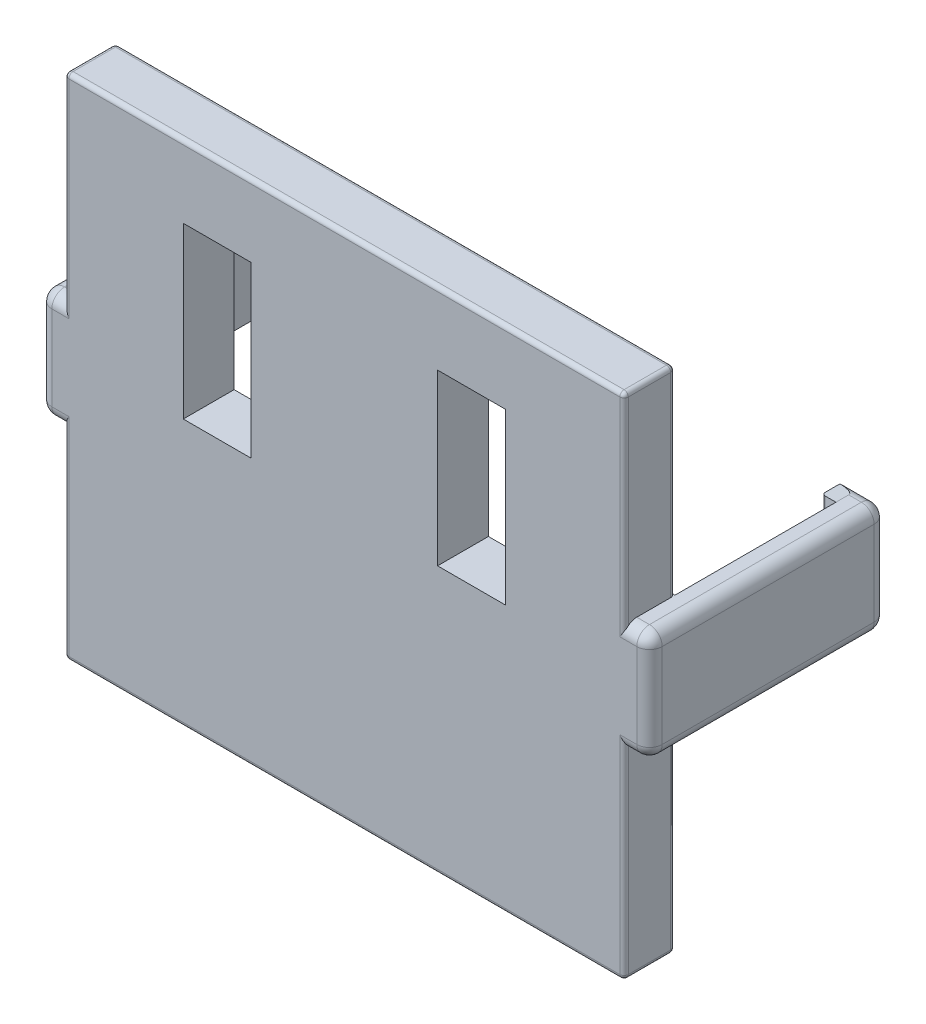
SolidWorks part; units mm, degrees
ref_plane "Plan de face" through (0, 0, 0) normal (0, 0, 1) x (1, 0, 0)
ref_plane "Plan de dessus" through (0, 0, 0) normal (0, 1, 0) x (1, 0, 0)
ref_plane "Plan de droite" through (0, 0, 0) normal (1, 0, 0) x (0, 0, -1)
sketch "Esquisse1" plane through (0, 0, 0) normal (0, 0, 1) x (1, 0, 0)
  line L1 (-16.5, 15) -> (16.5, 15)
  line L2 (-16.5, 15) -> (-16.5, -15)
  line L3 (-16.5, -15) -> (16.5, -15)
  line L4 (16.5, 15) -> (16.5, -15)
  line L5 (-16.5, 15) -> (16.5, -15) construction
  line L6 (-16.5, -15) -> (16.5, 15) construction
  point P0 (0, 0)
  dimension "D1" = 33
  dimension "D2" = 30
extrude "Boss.-Extru.1" add sketch "Esquisse1" along normal blind 3
sketch "Esquisse2" plane through (16.5, 0, 0) normal (1, 0, 0) x (0, 0, -1)
  line L0 (-3, -15) -> (-3, 15) construction
  line L1 (-3, 3.25) -> (11, 3.25)
  line L2 (-3, 3.25) -> (-3, -3.25)
  line L3 (-3, -3.25) -> (11, -3.25)
  line L4 (11, 3.25) -> (11, -3.25)
  line L5 (-3, -15) -> (0, -15) construction
  dimension "D1" = 11.75
  dimension "D2" = 6.5
  dimension "D3" = 14
extrude "Boss.-Extru.2" add sketch "Esquisse2" along normal blind 1.5
sketch "Esquisse3" plane through (16.5, 0, 0) normal (-1, 0, 0) x (0, 0, 1)
  line L0 (0, -3.25) -> (-11, -3.25) construction
  line L1 (-11, 3.25) -> (-9.5, 3.25)
  line L2 (-11, 3.25) -> (-11, -3.25)
  line L3 (-11, -3.25) -> (-9.5, -3.25)
  line L4 (-9.5, 3.25) -> (-9.5, -3.25)
  dimension "D1" = 1.5
extrude "Boss.-Extru.3" add sketch "Esquisse3" along normal blind 1 draft 10
fillet "Congé1" radius 0.75 1 edges at (18, -3.25, -4)
fillet "Congé2" radius 0.75 1 edges at (18, 3.25, -4)
fillet "Congé3" radius 0.75 5 edges at (17.7803, 3.0303, 3) (17.7803, -3.0303, 3) (18, 0, 3)
fillet "Congé4" radius 0.75 5 edges at (16.875, -3.25, -11) (17.7803, -3.0303, -11) (16.875, 3.25, -11) (17.7803, 3.0303, -11) (18, 0, -11)
fillet "Congé5" radius 0.25 1 edges at (15.5, 0, -10.8237)
fillet "Congé6" radius 0.25 1 edges at (15.5, 0, -9.6763)
sketch "Esquisse4" plane through (-16.5, 0, 0) normal (-1, 0, 0) x (0, 0, 1)
  line L0 (3, 15) -> (3, -15) construction
  line L1 (3, 3.25) -> (-11, 3.25)
  line L2 (3, 3.25) -> (3, -3.25)
  line L3 (3, -3.25) -> (-11, -3.25)
  line L4 (-11, 3.25) -> (-11, -3.25)
  line L5 (3, 15) -> (0, 15) construction
  line L6 (3, -15) -> (0, -15) construction
  dimension "D1" = 14
  dimension "D2" = 6.5
  dimension "D3" = 11.75
  dimension "D4" = 11.75
extrude "Boss.-Extru.4" add sketch "Esquisse4" along normal blind 1.5
sketch "Esquisse5" plane through (-16.5, 0, 0) normal (1, 0, 0) x (0, 0, -1)
  line L0 (11, -3.25) -> (0, -3.25) construction
  line L1 (11, 3.25) -> (9.5, 3.25)
  line L2 (11, 3.25) -> (11, -3.25)
  line L3 (11, -3.25) -> (9.5, -3.25)
  line L4 (9.5, 3.25) -> (9.5, -3.25)
  dimension "D1" = 1.5
extrude "Boss.-Extru.6" add sketch "Esquisse5" along normal blind 1 draft 10
fillet "Congé16" radius 0.75 1 edges at (-18, 0, 3)
fillet "Congé17" radius 0.75 3 edges at (-17.7803, -3.25, 2.7803) (-18, -3.25, -4.375)
fillet "Congé18" radius 0.75 3 edges at (-17.7803, 3.25, 2.7803) (-18, 3.25, -4.375)
fillet "Congé19" radius 0.75 5 edges at (-16.875, 3.25, -11) (-17.7803, 3.0303, -11) (-16.875, -3.25, -11) (-17.7803, -3.0303, -11) (-18, 0, -11)
fillet "Congé20" radius 0.25 1 edges at (-15.5, 0, -10.8237)
fillet "Congé21" radius 0.25 1 edges at (-15.5, 0, -9.6763)
fillet "Congé22" radius 0.25 1 edges at (0, 15, 0)
fillet "Congé23" radius 0.25 1 edges at (0, 15, 3)
fillet "Congé24" radius 0.25 5 edges at (16.5, 9, 0) (16.5, 14.9268, 0.0732) (16.5, 15, 1.5) (16.5, 14.9268, 2.9268)
fillet "Congé25" radius 0.25 3 edges at (16.5, -15, 1.5) (16.5, -9.125, 0)
fillet "Congé26" radius 0.25 12 edges at (-16.5, 14.9268, 2.9268) (-16.5, 15, 1.5) (-16.5, 14.9268, 0.0732) (16.4268, -14.9268, 2.9268) (16.4268, -14.9268, 0.0732) (-16.5, 9, 0) (-16.5, -9.125, 0) (-16.5, -15, 1.5) (-0.125, -15, 3) (-0.125, -15, 0)
sketch "Esquisse7" plane through (0, 0, 3) normal (0, 0, 1) x (1, 0, 0)
  line L0 (-16.25, 14.75) -> (-16.25, 2.5) construction
  line L1 (16.25, 14.75) -> (-16.25, 14.75) construction
  line L4 (-9.5, 10.75) -> (-9.5, 0.75)
  line L5 (-9.5, 0.75) -> (-5.5, 0.75)
  line L6 (-9.5, 10.75) -> (-5.5, 10.75)
  line L7 (-5.5, 10.75) -> (-5.5, 0.75)
  line L8 (-5.5, 10.75) -> (5.5, 10.75) construction
  line L9 (16.25, 2.5) -> (16.25, 14.75) construction
  line L10 (5.5, 10.75) -> (9.5, 10.75)
  line L11 (5.5, 10.75) -> (5.5, 0.75)
  line L12 (5.5, 0.75) -> (9.5, 0.75)
  line L13 (9.5, 10.75) -> (9.5, 0.75)
  dimension "D1" = 10
  dimension "D2" = 10
  dimension "D3" = 4
  dimension "D4" = 11
  dimension "D5" = 4
  dimension "D6" = 6.75
  dimension "D7" = 6.75
  dimension "D8" = 4
extrude "Enlèv. mat.-Extru.1" cut sketch "Esquisse7" against normal through all
